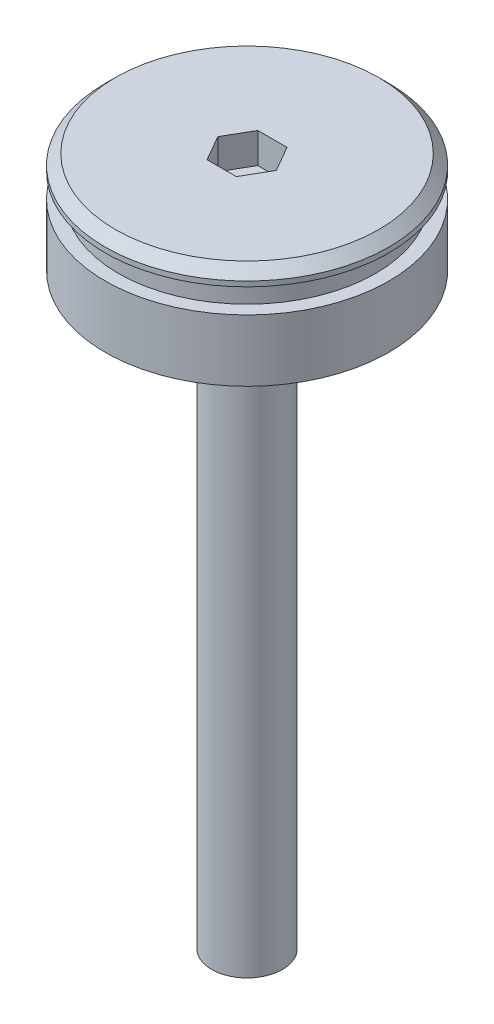
SolidWorks part; units mm, degrees
material "6061-T6 (SS)"
ref_plane "Piano frontale" through (0, 0, 0) normal (0, 0, 1) x (1, 0, 0)
ref_plane "Piano superiore" through (0, 0, 0) normal (0, 1, 0) x (1, 0, 0)
ref_plane "Piano destro" through (0, 0, 0) normal (1, 0, 0) x (0, 0, -1)
sketch "Schizzo1" plane through (0, 0, 0) normal (0, 0, 1) x (1, 0, 0)
  line L0 (0, 0) -> (0, 68)
  line L1 (0, 0) -> (-3.5, 0)
  line L2 (-3.5, 0) -> (-3.5, 58)
  line L3 (-3.5, 58) -> (-14, 58)
  line L4 (-14, 58) -> (-14, 68)
  line L5 (-14, 68) -> (0, 68)
  line L6 (0, 0) -> (0, 44.4338) construction
  line L10 (-14, 66.5) -> (-12.7, 66.5)
  line L11 (-12.7, 66.5) -> (-12.7, 64.1)
  line L12 (-12.7, 64.1) -> (-14, 64.1)
  dimension "D1" = 7
  dimension "D2" = 28
  dimension "D3" = 10
  dimension "D4" = 58
  dimension "D5" = 2.4
  dimension "D6" = 1.3
  dimension "D10" = 1.5
revolve "Rivoluzione1" add sketch "Schizzo1" angle 360 about L6 region at (-1.75, 0.6943, 0)
cosmetic thread "Filettatura cosmetica1" parameters "D1"=6, "D2"=4.891
chamfer "Smusso1" distance 1 angle 45 1 edges at (0, 68, -14)
sketch "Schizzo2" plane through (0, 68, 0) normal (0, 1, 0) x (1, 0, 0)
  line L6 (-2.8868, 0) -> (-1.4434, 2.5)
  line L7 (-1.4434, 2.5) -> (1.4434, 2.5)
  line L8 (1.4434, 2.5) -> (2.8868, 0)
  line L9 (2.8868, 0) -> (1.4434, -2.5)
  line L10 (1.4434, -2.5) -> (-1.4434, -2.5)
  line L11 (-1.4434, -2.5) -> (-2.8868, 0)
  circle A0 centre (0, 0) radius 2.8868
  dimension "D1" = 5
extrude "Taglio-Estrusione1" cut sketch "Schizzo2" against normal blind 3 contours L11 L10 L9 L8 L7 L6 region at (0, 68, 0)
ref_plane "Piano1" through (0, 0, -14) normal (0, 0, -1) x (-1, 0, 0)
sketch "Schizzo4" plane through (0, 0, -14) normal (0, 0, -1) x (-1, 0, 0)
  circle A0 centre (0, 62) radius 1.5
  circle A1 centre (0, 62) radius 1.5 construction
extrude "Taglio-Estrusione3" cut sketch "Schizzo4" against normal blind 8
